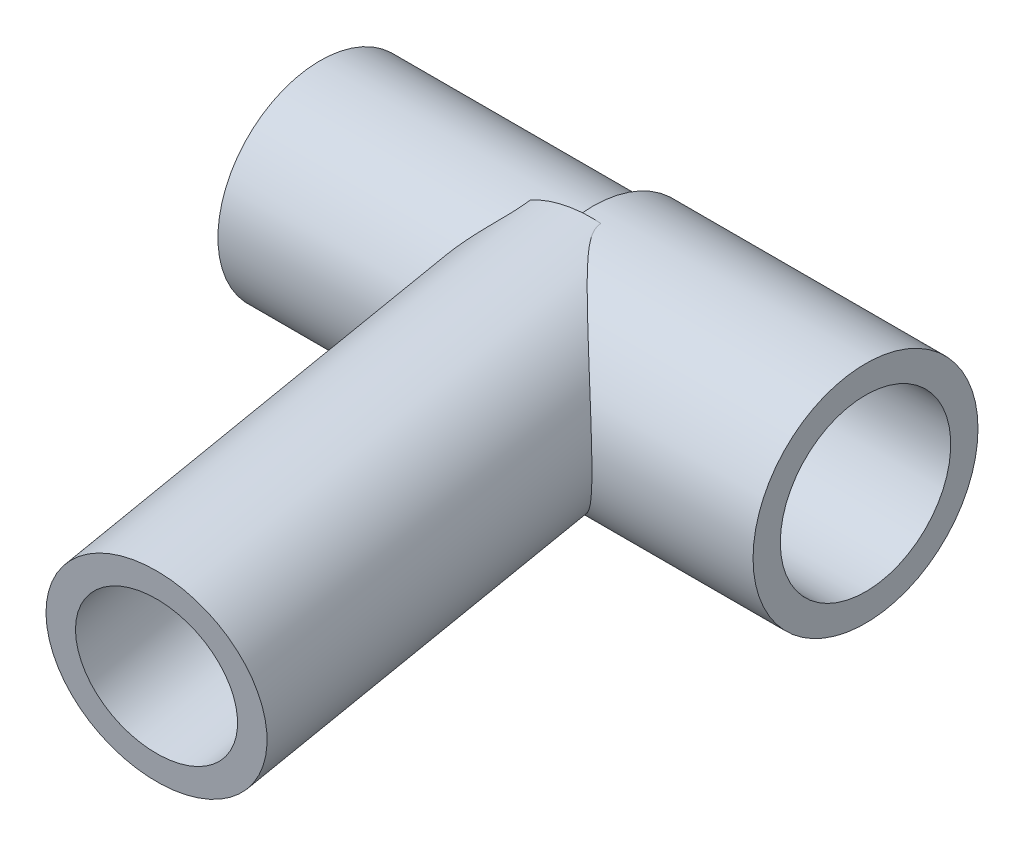
SolidWorks part; units mm, degrees
ref_plane "Front Plane" through (0, 0, 0) normal (0, 0, 1) x (1, 0, 0)
ref_plane "Plane_top" through (0, 0, 0) normal (0, 1, 0) x (1, 0, 0)
ref_plane "Right Plane" through (0, 0, 0) normal (1, 0, 0) x (0, 0, -1)
sketch "Sketch1" plane through (0, 0, 0) normal (0, 1, 0) x (1, 0, 0)
  line L0 (-470.9414, 0) -> (529.0586, 0) construction
  dimension "D1" = 1000
ref_plane "Plane_lower" through (0, -100, 0) normal (0, 1, 0) x (1, 0, 0)
sketch "Sketch2" plane through (0, -100, 0) normal (0, 1, 0) x (1, 0, 0)
  line L0 (0, 0) -> (0, -940) construction
  line L1 (0, -940) -> (25, -940) construction
  dimension "D1" = 940
  dimension "D2" = 25
ref_plane "Real_plane" through (0, 0, 0) normal (0, 0.9944, 0.1058) x (1, 0, 0)
sketch "Sketch5" plane through (0, 0, 0) normal (0, 1, 0) x (1, 0, 0)
  line L0 (0, 0) -> (0, 16.5) construction
  line L1 (0, 16.5) -> (69.3947, 16.5) construction
  line L4 (40, 4) -> (0, 4)
  line L5 (40, 0) -> (0, 0)
  line L6 (0, 0) -> (0, 4)
  line L7 (40, 0) -> (40, 4)
  dimension "D1" = 16.5
  dimension "D2" = 4
  dimension "D3" = 40
revolve "Revolve2" add sketch "Sketch5" angle 360 about L1
sketch "Sketch6" plane through (0, 0, 0) normal (0, 1, 0) x (1, 0, 0)
  line L0 (0, 16.5) -> (-48.3518, 16.5) construction
  line L1 (0, 33) -> (0, 0) construction
  line L3 (0, 5.5) -> (-40, 5.5)
  line L9 (-40, 5.5) -> (-40, 1.5)
  line L10 (-40, 1.5) -> (0, 1.5)
  line L11 (0, 1.5) -> (0, 5.5)
  dimension "D1" = 11
  dimension "D2" = 4
  dimension "D3" = 40
revolve "Revolve4" add sketch "Sketch6" angle 360 about L0
sketch "Sketch8" plane through (0, 0, 0) normal (0, 0.9944, 0.1058) x (1, 0, 0)
  line L0 (0, 16.4074) -> (0, -923.5926) construction
  line L1 (0, 31.4074) -> (0, 1.4074) construction
  line L2 (0, -923.5926) -> (75, -923.5926) construction
  line L3 (0, 16.4074) -> (75, -923.5926) construction
  line L4 (75, -923.5926) -> (96.9303, -921.8428) construction
  line L5 (0, 16.4074) -> (10.9652, 17.2823) construction
  line L9 (14.9525, 17.6004) -> (10.9652, 17.2823)
  line L10 (10.9652, 17.2823) -> (16.5326, -52.496)
  line L11 (16.5326, -52.496) -> (20.5199, -52.1778)
  line L12 (20.5199, -52.1778) -> (14.9525, 17.6004)
  dimension "D1" = 940
  dimension "D2" = 75
  dimension "D3" = 22
  dimension "D4" = 11
  dimension "D5" = 4
  dimension "D6" = 70
revolve "Revolve5" add sketch "Sketch8" angle 360 about L3
